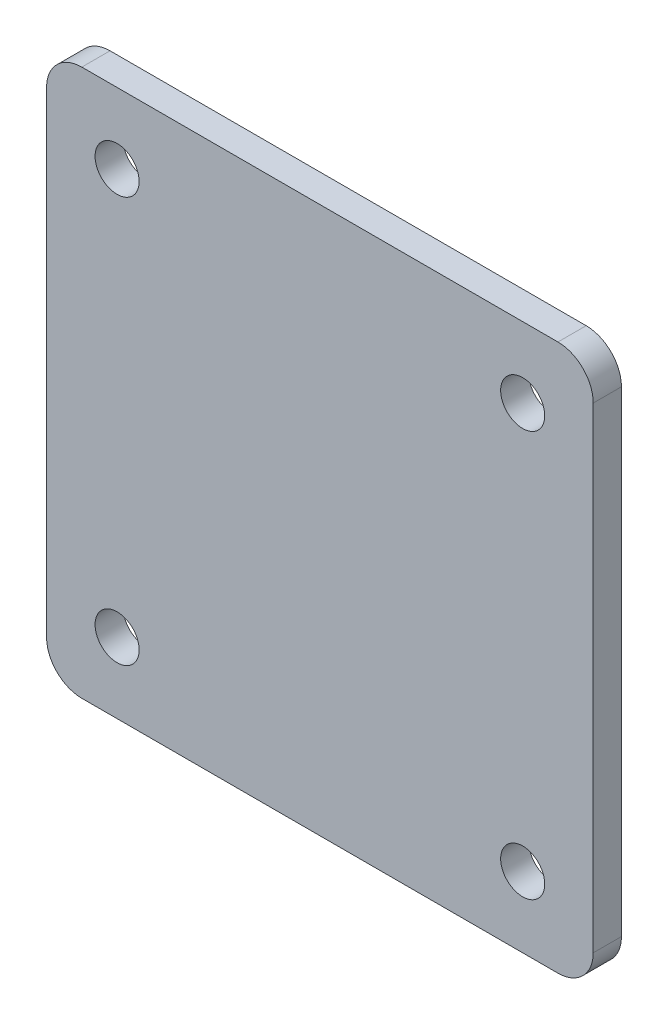
SolidWorks part; units mm, degrees
ref_plane "Front Plane" through (0, 0, 0) normal (0, 0, 1) x (1, 0, 0)
ref_plane "Top Plane" through (0, 0, 0) normal (0, 1, 0) x (1, 0, 0)
ref_plane "Right Plane" through (0, 0, 0) normal (1, 0, 0) x (0, 0, -1)
sketch "Sketch1" plane through (0, 0, 0) normal (0, 0, 1) x (1, 0, 0)
  line L1 (-13.5, -15.5) -> (13.5, -15.5)
  line L2 (-15.5, -13.5) -> (-15.5, 13.5)
  line L3 (-13.5, 15.5) -> (13.5, 15.5)
  line L4 (15.5, -13.5) -> (15.5, 13.5)
  arc A0 (-13.5, -15.5) -> (-15.5, -13.5) centre (-13.5, -13.5) cw
  arc A1 (13.5, -15.5) -> (15.5, -13.5) centre (13.5, -13.5) ccw
  arc A2 (13.5, 15.5) -> (15.5, 13.5) centre (13.5, 13.5) cw
  arc A3 (-15.5, 13.5) -> (-13.5, 15.5) centre (-13.5, 13.5) cw
  point P4 (-15.5, 0)
  point P6 (0, 15.5)
  point P9 (-15.5, -15.5)
  point P16 (-15.5, 15.5)
  dimension "D2" = 2
  dimension "D1" = 31
extrude "Boss-Extrude1" add sketch "Sketch1" along normal blind 1.6
hole_wizard "Ø2.5mm Dowel Hole1" positions "Sketch2" profile "Sketch3" hole size "Ø2.5" standard "ANSI Metric" end condition through all
sketch "Sketch2" plane through (0, 0, 1.6) normal (0, 0, 1) x (1, 0, 0)
  line L0 (-11.5, -11.5) -> (-11.5, 11.5) construction
  line L1 (-11.5, 11.5) -> (11.5, 11.5) construction
  line L2 (11.5, 11.5) -> (11.5, -11.5) construction
  line L3 (11.5, -11.5) -> (-11.5, -11.5) construction
  point P0 (-11.5, 11.5)
  point P2 (11.5, 11.5)
  point P4 (11.5, -11.5)
  point P6 (-11.5, -11.5)
  point P18 (0, -11.5)
  point P20 (-11.5, 0)
  dimension "D1" = 23
sketch "Sketch3" plane through (-11.5, 11.5, 1.6) normal (1, 0, 0) x (0, -1, 0)
  line L0 (0, 0) -> (0, 1.6)
  line L1 (0, 1.6) -> (1.25, 1.6)
  line L2 (1.25, 1.6) -> (1.25, 0)
  line L5 (1.25, 0) -> (0, 0)
  line L11 (0, -6.35) -> (0, 107.95) construction
  dimension "Thru Hole Dia." = 2.5
  dimension "Thru Hole Depth" = 1.6
